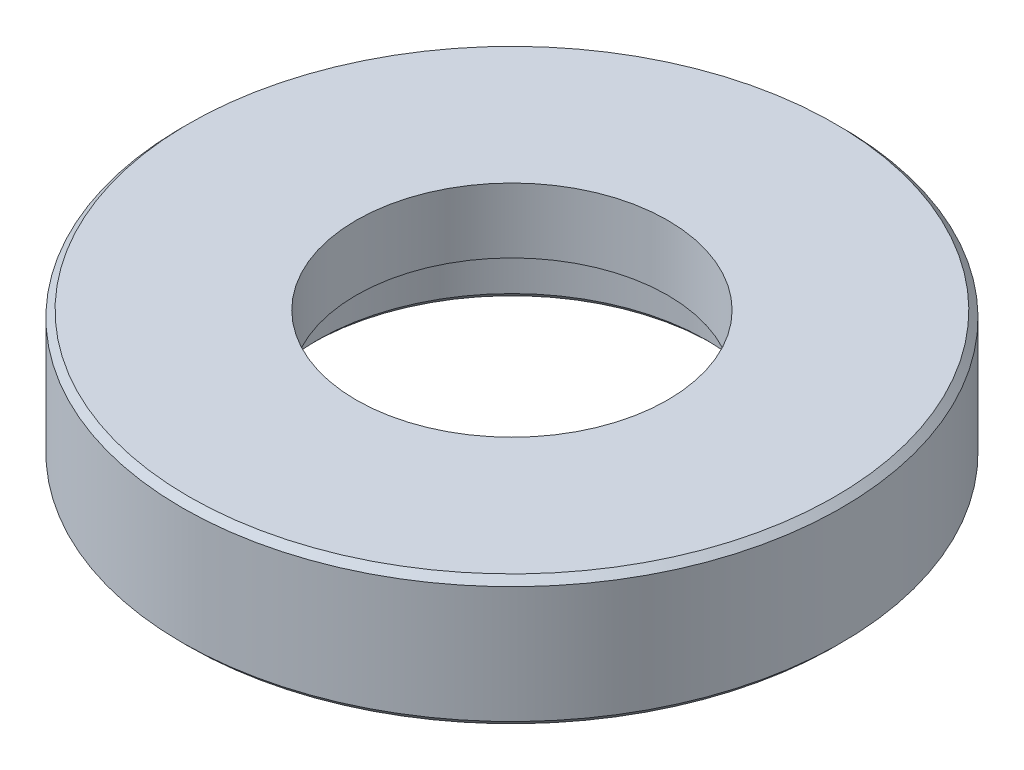
SolidWorks part; units mm, degrees
ref_plane "Front Plane" through (0, 0, 0) normal (0, 0, 1) x (1, 0, 0)
ref_plane "Top Plane" through (0, 0, 0) normal (0, 1, 0) x (1, 0, 0)
ref_plane "Right Plane" through (0, 0, 0) normal (1, 0, 0) x (0, 0, -1)
sketch "Sketch1" plane through (0, 0, 0) normal (0, 1, 0) x (1, 0, 0)
  circle A0 centre (0, 0) radius 6
  circle A1 centre (0, 0) radius 7.5
  circle A2 centre (0, 0) radius 12.7
extrude "Boss-Extrude1" add sketch "Sketch1" along normal blind 5 contours A2
extrude "Cut-Extrude1" cut sketch "Sketch1<3>" along normal up to surface (5 mm away) contours A0 up to face at (0, 5, 12.7)
sketch "Sketch1<3>" plane through (0, 0, 0) normal (0, 1, 0) x (1, 0, 0) same geometry as "Sketch1"
extrude "Cut-Extrude2" cut sketch "Sketch1<4>" along normal blind 2.5 contours A1 A0 region at (-7.2879, 0, 0)
sketch "Sketch1<4>" plane through (0, 0, 0) normal (0, 1, 0) x (1, 0, 0) same geometry as "Sketch1"
chamfer "Chamfer1" distance 0.25 angle 45 3 edges at (0, 5, 12.7) (0, 0, 7.5) (0, 0, 12.7)
